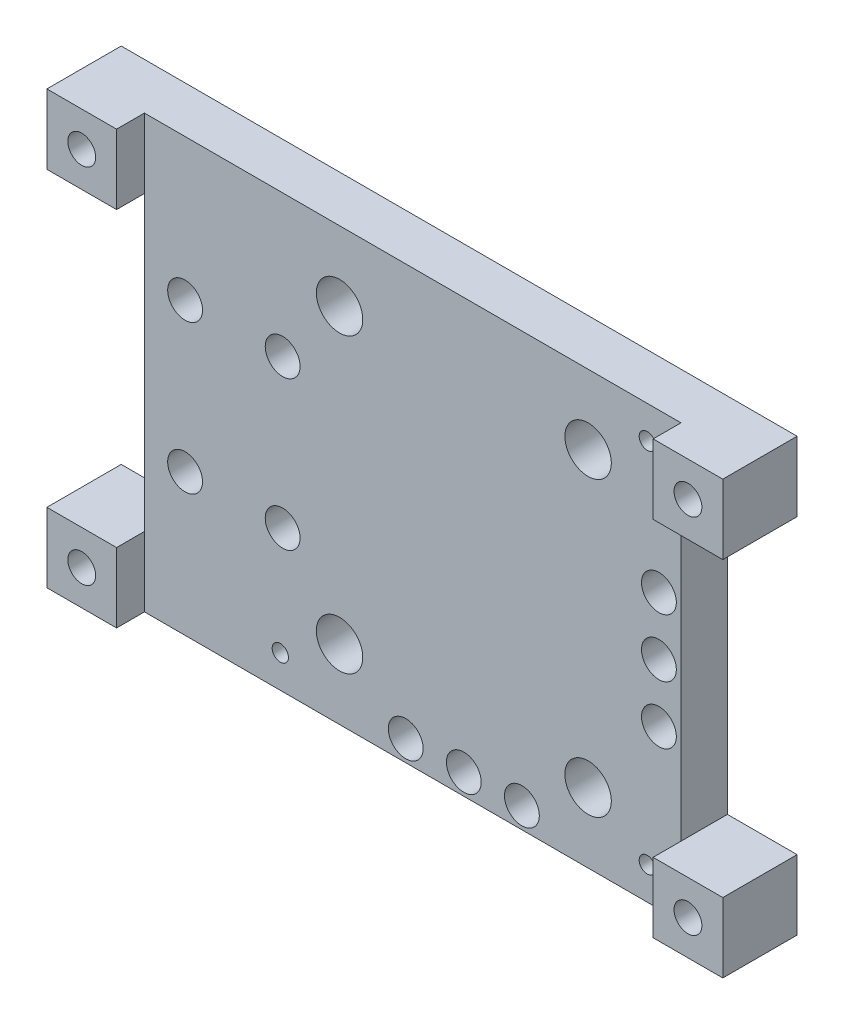
SolidWorks part; units mm, degrees
ref_plane "前视基准面" through (0, 0, 0) normal (0, 0, 1) x (1, 0, 0)
ref_plane "上视基准面" through (0, 0, 0) normal (0, 1, 0) x (1, 0, 0)
ref_plane "右视基准面" through (0, 0, 0) normal (1, 0, 0) x (0, 0, -1)
other "Configuration Table"
sketch "草图1" plane through (0, 0, 0) normal (0, 0, 1) x (1, 0, 0)
  line L5 (-11.55, 9.3) -> (11.55, 9.3)
  line L6 (-11.55, 9.3) -> (-11.55, -9.3)
  line L7 (-11.55, -9.3) -> (11.55, -9.3)
  line L8 (11.55, 9.3) -> (11.55, -9.3)
  point P4 (0, 9.3)
  point P12 (-11.55, 0)
  dimension "D3" = 23.1
  dimension "D4" = 18.6
extrude "凸台-拉伸1" add sketch "草图1" along normal blind 2 contours L6 L7 L8 L5
sketch "草图2" plane through (0, 0, 0) normal (0, 0, -1) x (-1, 0, 0)
  circle A0 centre (-10.6, 2.5) radius 0.75
  circle A1 centre (-10.6, 0) radius 0.75
  circle A2 centre (-10.6, -2.5) radius 0.75
  circle A3 centre (-7.55, -6.3) radius 1
  circle A4 centre (3.15, -6.3) radius 1
  circle A5 centre (-4.7, -8.4) radius 0.75
  circle A6 centre (-2.2, -8.4) radius 0.75
  circle A7 centre (0.3, -8.4) radius 0.75
  circle A8 centre (-7.55, 6.3) radius 1
  circle A9 centre (3.15, 6.3) radius 1
  circle A10 centre (5.6, 3.2) radius 0.75
  circle A11 centre (9.8, 3.2) radius 0.75
  circle A12 centre (5.6, -3.2) radius 0.75
  circle A13 centre (9.8, -3.2) radius 0.75
  circle A14 centre (5.7, -7.9) radius 0.35
  circle A15 centre (-10.1, -7.9) radius 0.35
  circle A16 centre (-10.1, 7.9) radius 0.35
  point P30 (0, 0)
  point P33 (0, 0)
  point P36 (0, 0)
  point P37 (0, 0)
  point P38 (0, 0)
  dimension "D1" = 0.7
  dimension "D2" = 2
  dimension "D3" = 1.5
extrude "切除-拉伸1" cut sketch "草图2" against normal through all contours A15 | A3 | A2 | A1 | A0 | A8 | A16 | A9 | A10 | A11 | A13 | A12 | A4 | A14 | A7 | A6 | A5
sketch "草图3" plane through (0, 0, 0) normal (0, 0, -1) x (-1, 0, 0)
  line L1 (-11.55, 9.3) -> (-14.55, 9.3)
  line L2 (-11.55, 9.3) -> (-11.55, 6.3)
  line L3 (-11.55, 6.3) -> (-14.55, 6.3)
  line L4 (-14.55, 9.3) -> (-14.55, 6.3)
  line L5 (-11.55, -9.3) -> (-14.55, -9.3)
  line L6 (-11.55, -9.3) -> (-11.55, -6.3)
  line L7 (-11.55, -6.3) -> (-14.55, -6.3)
  line L8 (-14.55, -9.3) -> (-14.55, -6.3)
  line L9 (11.55, 9.3) -> (14.55, 9.3)
  line L10 (11.55, 9.3) -> (11.55, 6.3)
  line L11 (11.55, 6.3) -> (14.55, 6.3)
  line L12 (14.55, 9.3) -> (14.55, 6.3)
  line L13 (11.55, -9.3) -> (14.55, -9.3)
  line L14 (11.55, -9.3) -> (11.55, -6.3)
  line L15 (11.55, -6.3) -> (14.55, -6.3)
  line L16 (14.55, -9.3) -> (14.55, -6.3)
  circle A0 centre (-13.05, 7.8) radius 1
  circle A1 centre (-13.05, -7.8) radius 1
  circle A2 centre (13.05, -7.8) radius 1
  circle A3 centre (13.05, -7.8) radius 0.6
  circle A4 centre (13.05, 7.8) radius 1
  circle A5 centre (13.05, 7.8) radius 0.6
  circle A6 centre (-13.05, -7.8) radius 0.6
  circle A7 centre (-13.05, 7.8) radius 0.6
  point P32 (-13.05, -9.3)
  point P33 (-14.55, -7.8)
  point P34 (13.1618, 7.7551)
  point P35 (13.05, 9.3)
  point P36 (14.55, 7.8)
  point P37 (0, 0)
  point P38 (0, 0)
  point P39 (-16.6105, -7.9227)
  point P40 (0, 0)
  point P41 (0, 0)
  point P42 (0, 0)
  point P43 (0, 0)
  dimension "D3" = 1.2
  dimension "D4" = 2
  dimension "D1" = 3
  dimension "D2" = 3
extrude "凸台-拉伸2" add sketch "草图3" against normal blind 3.2 contours L5 L8 L7 L6 | L3 L4 L1 L2 | L11 L12 L9 L10 | L15 L16 L13 L14 | A6 | A7 | A5 | A3
extrude "切除-拉伸2" cut sketch "草图3<3>" against normal blind 1.5 contours A0 | A4 | A2 | A1
sketch "草图3<3>" plane through (0, 0, 0) normal (0, 0, -1) x (-1, 0, 0) same geometry as "草图3"
